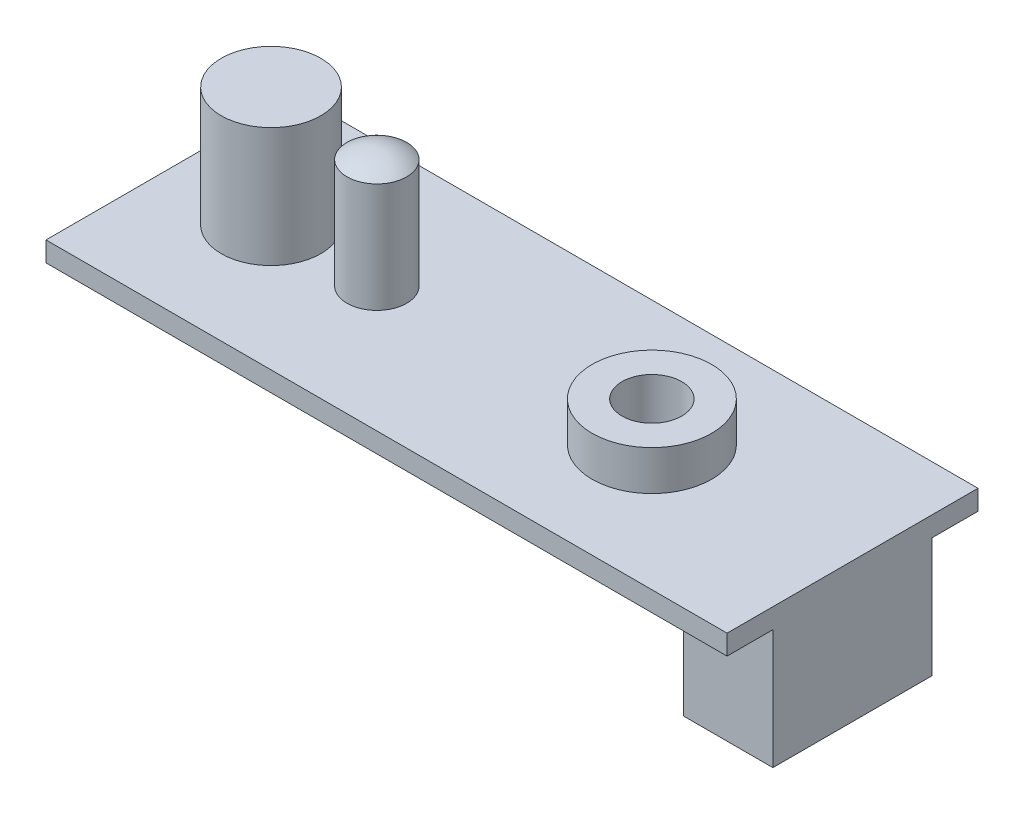
SolidWorks part; units mm, degrees
ref_plane "前视基准面" through (0, 0, 0) normal (0, 0, 1) x (1, 0, 0)
ref_plane "上视基准面" through (0, 0, 0) normal (0, 1, 0) x (1, 0, 0)
ref_plane "右视基准面" through (0, 0, 0) normal (1, 0, 0) x (0, 0, -1)
sketch "草图1" plane through (0, 0, 0) normal (0, 1, 0) x (1, 0, 0)
  line L1 (-17.1, 6.3) -> (17.1, 6.3)
  line L2 (-17.1, 6.3) -> (-17.1, -6.3)
  line L3 (-17.1, -6.3) -> (17.1, -6.3)
  line L4 (17.1, 6.3) -> (17.1, -6.3)
  line L5 (-17.1, 6.3) -> (17.1, -6.3) construction
  line L6 (-17.1, -6.3) -> (17.1, 6.3) construction
  point P0 (0, 0)
  dimension "D1" = 34.2
  dimension "D2" = 12.6
extrude "凸台-拉伸1" add sketch "草图1" along normal blind 1
sketch "草图2" plane through (0, 1, 0) normal (0, 1, 0) x (1, 0, 0)
  line L0 (-17.1, 0) -> (17.1, 0) construction
  line L1 (-17.1, 6.3) -> (-17.1, -6.3) construction
  line L2 (17.1, -6.3) -> (17.1, 6.3) construction
  circle A0 centre (-12.1, 0) radius 2.5
  dimension "D1" = 5
extrude "凸台-拉伸2" add sketch "草图2" along normal blind 6
sketch "草图3" plane through (0, 1, 0) normal (0, 1, 0) x (1, 0, 0)
  line L1 (-17.1, 6.3) -> (-17.1, -6.3) construction
  line L2 (-17.1, 0) -> (17.1, 0) construction
  line L3 (17.1, -6.3) -> (17.1, 6.3) construction
  circle A2 centre (-6.7862, 0) radius 1.5
extrude "凸台-拉伸3" add sketch "草图3" along normal blind 5.5
dome "圆顶3" faces to dome 1 distance 0.5 reverse direction no elliptical dome no face at (-6.7862, 6.5, 1.5) parameters "D1"=0.5
sketch "草图4" plane through (0, 1, 0) normal (0, 1, 0) x (1, 0, 0)
  circle A0 centre (7.0245, 0) radius 1.5
extrude "切除-拉伸1" cut sketch "草图4" against normal through all
sketch "草图5" plane through (0, 1, 0) normal (0, 1, 0) x (1, 0, 0)
  circle A0 centre (7.0245, 0) radius 3
  circle A1 centre (7.0245, 0) radius 1.5
extrude "凸台-拉伸4" add sketch "草图5" along normal blind 2
sketch "草图6" plane through (0, 0, 0) normal (0, -1, 0) x (-1, 0, 0)
  line L0 (17.1, 0) -> (-17.1, 0) construction
  line L1 (17.1, 6.3) -> (17.1, -6.3) construction
  line L2 (-17.1, -6.3) -> (-17.1, 6.3) construction
  line L10 (-17.1, 4) -> (-17.1, -4)
  line L11 (-12.6, 4) -> (-17.1, 4)
  line L12 (-12.6, -4) -> (-12.6, 4)
  line L13 (-17.1, -4) -> (-12.6, -4)
extrude "凸台-拉伸6" add sketch "草图6" along normal blind 6
sketch "草图7" plane through (0, -6, 0) normal (0, -1, 0) x (1, 0, 0)
  line L0 (14.85, 4) -> (14.85, -4) construction
  line L1 (17.1, 4) -> (12.6, 4) construction
  line L2 (12.6, -4) -> (17.1, -4) construction
  line L4 (13.1584, 3.2492) -> (16.5416, 3.2492)
  line L5 (13.1584, 3.2492) -> (13.1584, -3.2492)
  line L6 (13.1584, -3.2492) -> (16.5416, -3.2492)
  line L7 (16.5416, 3.2492) -> (16.5416, -3.2492)
  line L8 (13.1584, 3.2492) -> (16.5416, -3.2492) construction
  line L9 (13.1584, -3.2492) -> (16.5416, 3.2492) construction
  point P6 (14.85, 0)
extrude "切除-拉伸2" cut sketch "草图7" against normal blind 5
